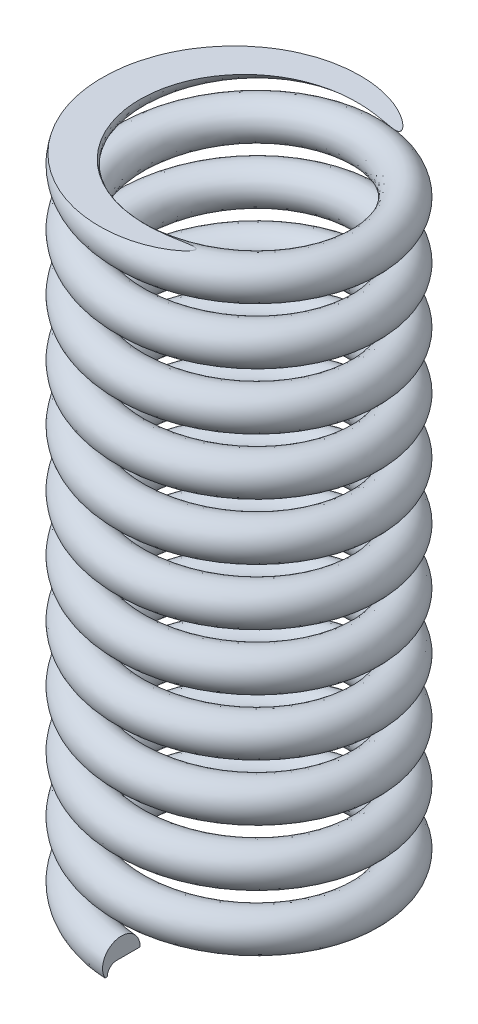
SolidWorks part; units mm, degrees
note: '?' marks a value the reader was unsure of.
ref_plane "Спереди" through (0, 0, 0) normal (0, 0, 1) x (1, 0, 0)
ref_plane "Сверху" through (0, 0, 0) normal (0, 1, 0) x (1, 0, 0)
ref_plane "Справа" through (0, 0, 0) normal (1, 0, 0) x (0, 0, -1)
other "Configuration Table"
sketch "Эскиз1" plane through (0, 0, 0) normal (0, 1, 0) x (1, 0, 0)
  circle A0 centre (0, 0) radius 12.5
  dimension "D1" = 25
curve "Спираль1" pitch 6 height 70 turns 11.6667
sketch "Эскиз2" plane through (0, 0, 0) normal (1, 0, 0) x (0, 0, -1)
  circle A0 centre (-12.5, 0) radius 2
  spline S0 degree 3 poles (-12.5, 0) (-12.5, 0.1246) (-11.8444, 0.3767) (-9.045, 0.7526) (-4.8589, 1.1291) (0.0722, 1.5054) (4.9923, 1.8817) (9.1469, 2.2581) (11.8991, 2.6344) (12.827, 3.0108) (11.7882, 3.3871) (8.9421, 3.7634) (4.7249, 4.1398) (-0.2167, 4.5161) (-5.125, 4.8925) (-9.2476, 5.2688) (-11.9523, 5.6452) (-12.8245, 6.0215) (-11.7305, 6.3978) (-8.8379, 6.7742) (-4.5903, 7.1505) (0.3611, 7.5269) (5.2571, 7.9032) (9.3471, 8.2796) (12.004, 8.6559) (12.8205, 9.0323) (11.6713, 9.4086) (8.7327, 9.7849) (4.4552, 10.1613) (-0.5054, 10.5376) (-5.3885, 10.914) (-9.4454, 11.2903) (-12.0542, 11.6667) (-12.8148, 12.043) (-11.6106, 12.4194) (-8.6263, 12.7957) (-4.3194, 13.172) (0.6497, 13.5484) (5.5192, 13.9247) (9.5426, 14.3011) (12.1028, 14.6774) (12.8075, 15.0538) (11.5485, 15.4301) (8.5189, 15.8065) (4.1831, 16.1828) (-0.7939, 16.5591) (-5.6493, 16.9355) (-9.6385, 17.3118) (-12.1499, 17.6882) (-12.7985, 18.0645) (-11.4849, 18.4409) (-8.4103, 18.8172) (-4.0463, 19.1935) (0.938, 19.5699) (5.7786, 19.9462) (9.7332, 20.3226) (12.1955, 20.6989) (12.788, 21.0753) (11.4198, 21.4516) (8.3007, 21.828) (3.909, 22.2043) (-1.082, 22.5806) (-5.9072, 22.957) (-9.8267, 23.3333) (-12.2395, 23.7097) (-12.7758, 24.086) (-11.3533, 24.4624) (-8.1901, 24.8387) (-3.7712, 25.2151) (1.2259, 25.5914) (6.035, 25.9677) (9.9189, 26.3441) (12.282, 26.7204) (12.762, 27.0968) (11.2853, 27.4731) (8.0784, 27.8495) (3.6329, 28.2258) (-1.3696, 28.6022) (-6.1621, 28.9785) (-10.0098, 29.3548) (-12.3229, 29.7312) (-12.7466, 30.1075) (-11.2159, 30.4839) (-7.9657, 30.8602) (-3.4941, 31.2366) (1.5131, 31.6129) (6.2884, 31.9892) (10.0995, 32.3656) (12.3622, 32.7419) (12.7295, 33.1183) (11.1451, 33.4946) (7.852, 33.871) (3.3549, 34.2473) (-1.6565, 34.6237) (-6.4139, 35) (-10.188, 35.3763) (-12.4, 35.7527) (-12.7109, 36.129) (-11.0729, 36.5054) (-7.7373, 36.8817) (-3.2153, 37.2581) (1.7996, 37.6344) (6.5386, 38.0108) (10.2751, 38.3871) (12.4362, 38.7634) (12.6906, 39.1398) (10.9993, 39.5161) (7.6216, 39.8925) (3.0753, 40.2688) (-1.9425, 40.6452) (-6.6624, 41.0215) (-10.3609, 41.3978) (-12.4708, 41.7742) (-12.6687, 42.1505) (-10.9243, 42.5269) (-7.5049, 42.9032) (-2.9349, 43.2796) (2.0851, 43.6559) (6.7854, 44.0323) (10.4454, 44.4086) (12.5039, 44.7849) (12.6453, 45.1613) (10.8479, 45.5376) (7.3873, 45.914) (2.7941, 46.2903) (-2.2275, 46.6667) (-6.9076, 47.043) (-10.5286, 47.4194) (-12.5353, 47.7957) (-12.6202, 48.172) (-10.7701, 48.5484) (-7.2687, 48.9247) (-2.6529, 49.3011) (2.3696, 49.6774) (7.0289, 50.0538) (10.6104, 50.4301) (12.5652, 50.8065) (12.5935, 51.1828) (10.6909, 51.5591) (7.1492, 51.9355) (2.5114, 52.3118) (-2.5114, 52.6882) (-7.1492, 53.0645) (-10.6909, 53.4409) (-12.5935, 53.8172) (-12.5652, 54.1935) (-10.6104, 54.5699) (-7.0289, 54.9462) (-2.3696, 55.3226) (2.6529, 55.6989) (7.2687, 56.0753) (10.7701, 56.4516) (12.6202, 56.828) (12.5353, 57.2043) (10.5286, 57.5806) (6.9076, 57.957) (2.2275, 58.3333) (-2.7941, 58.7097) (-7.3873, 59.086) (-10.8479, 59.4624) (-12.6453, 59.8387) (-12.5039, 60.2151) (-10.4454, 60.5914) (-6.7854, 60.9677) (-2.0851, 61.3441) (2.9349, 61.7204) (7.5049, 62.0968) (10.9243, 62.4731) (12.6687, 62.8495) (12.4708, 63.2258) (10.3609, 63.6022) (6.6624, 63.9785) (1.9425, 64.3548) (-3.0753, 64.7312) (-7.6216, 65.1075) (-10.9993, 65.4839) (-12.6906, 65.8602) (-12.4362, 66.2366) (-10.2751, 66.6129) (-6.5386, 66.9892) (-1.7996, 67.3656) (3.2153, 67.7419) (7.7373, 68.1183) (11.0728, 68.4946) (12.7112, 68.8709) (12.3989, 69.2474) (10.1921, 69.6233) (7.663, 69.8754) (6.25, 70) knots 0 0 0 0 0.005376 0.010753 0.016129 0.021505 0.026882 0.032258 0.037634 0.043011 0.048387 0.053763 0.05914 0.064516 0.069892 0.075269 0.080645 0.086022 0.091398 0.096774 0.102151 0.107527 0.112903 0.11828 0.123656 0.129032 0.134409 0.139785 0.145161 0.150538 0.155914 0.16129 0.166667 0.172043 0.177419 0.182796 0.188172 0.193548 0.198925 0.204301 0.209677 0.215054 0.22043 0.225806 0.231183 0.236559 0.241935 0.247312 0.252688 0.258065 0.263441 0.268817 0.274194 0.27957 0.284946 0.290323 0.295699 0.301075 0.306452 0.311828 0.317204 0.322581 0.327957 0.333333 0.33871 0.344086 0.349462 0.354839 0.360215 0.365591 0.370968 0.376344 0.38172 0.387097 0.392473 0.397849 0.403226 0.408602 0.413978 0.419355 0.424731 0.430108 0.435484 0.44086 0.446237 0.451613 0.456989 0.462366 0.467742 0.473118 0.478495 0.483871 0.489247 0.494624 0.5 0.505376 0.510753 0.516129 0.521505 0.526882 0.532258 0.537634 0.543011 0.548387 0.553763 0.55914 0.564516 0.569892 0.575269 0.580645 0.586022 0.591398 0.596774 0.602151 0.607527 0.612903 0.61828 0.623656 0.629032 0.634409 0.639785 0.645161 0.650538 0.655914 0.66129 0.666667 0.672043 0.677419 0.682796 0.688172 0.693548 0.698925 0.704301 0.709677 0.715054 0.72043 0.725806 0.731183 0.736559 0.741935 0.747312 0.752688 0.758065 0.763441 0.768817 0.774194 0.77957 0.784946 0.790323 0.795699 0.801075 0.806452 0.811828 0.817204 0.822581 0.827957 0.833333 0.83871 0.844086 0.849462 0.854839 0.860215 0.865591 0.870968 0.876344 0.88172 0.887097 0.892473 0.897849 0.903226 0.908602 0.913978 0.919355 0.924731 0.930108 0.935484 0.94086 0.946237 0.951613 0.956989 0.962366 0.967742 0.973118 0.978495 0.983871 0.989247 0.994624 1 1 1 1 construction
  dimension "D1" = 4
sweep "По траектории1" add profiles "Эскиз2" path "Спираль1"
ref_axis "Ось1" through (0, 50, 0) along (0, -1, 0)?
sketch "Эскиз4" plane through (0, 0, 0) normal (1, 0, 0) x (0, 0, -1)
  line L0 (0, 0) -> (-13, 0)
  line L1 (0, 67.5) -> (24.987, 67.5)
  line L2 (-14, -1) -> (-16.5304, -1)
  line L3 (-16.5304, -1) -> (-16.5304, -3.8234)
  line L4 (-16.5304, -3.8234) -> (0, -3.8234)
  line L5 (0, -3.8234) -> (0, 0)
  line L6 (24.987, 67.5) -> (24.987, 79.9449)
  line L7 (24.987, 79.9449) -> (0, 79.9449)
  line L8 (0, 79.9449) -> (0, 67.5)
  arc A0 (-13, 0) -> (-14, -1) centre (-13, -1) ccw
  dimension "D2" = 1
  dimension "D1" = 67.5
  dimension "D3" = 24.987
  dimension "D4" = 14
  dimension "D5" = 16.5304
  dimension "D6" = 79.9449
  dimension "D7" = 3.8234
revolve "Вырез-Повернуть1" cut sketch "Эскиз4" angle 360 about L8
